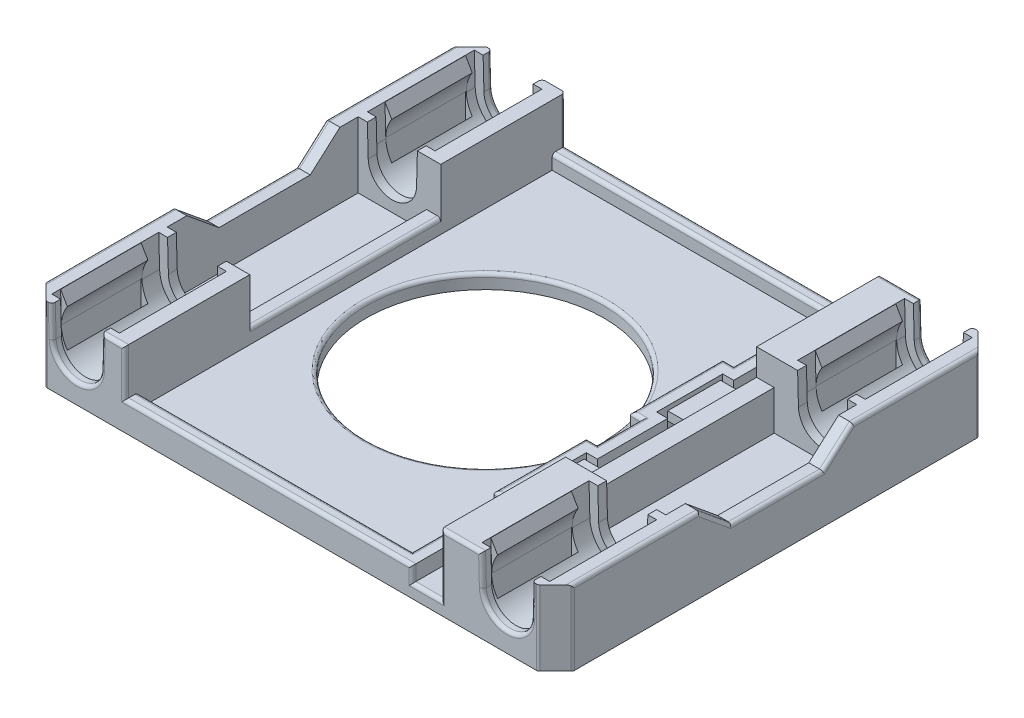
SolidWorks part; units mm, degrees
ref_plane "Front" through (0, 0, 0) normal (0, 0, 1) x (1, 0, 0)
ref_plane "Top" through (0, 0, 0) normal (0, 1, 0) x (1, 0, 0)
ref_plane "Right" through (0, 0, 0) normal (1, 0, 0) x (0, 0, -1)
sketch "Sketch1" plane through (0, 0, 0) normal (0, 1, 0) x (1, 0, 0)
  line L1 (-62.38, 50) -> (62.38, 50)
  line L2 (-62.38, 50) -> (-62.38, -50)
  line L3 (-62.38, -50) -> (62.38, -50)
  line L4 (62.38, 50) -> (62.38, -50)
  dimension "D1" = 124.76
  dimension "D2" = 100
  dimension "6" = 62.38
  dimension "D4" = 50
extrude "Boss-Extrude1" add sketch "Sketch1" along normal blind 20
sketch "Sketch2" plane through (0, 0, 50) normal (0, 0, 1) x (1, 0, 0)
  line L0 (-62.38, 0) -> (62.38, 0) construction
  line L1 (-62.38, 20) -> (-62.38, 0) construction
  line L2 (62.38, 20) -> (62.38, 0) construction
  circle A0 centre (-48.88, 10) radius 7.495
  circle A1 centre (48.88, 10) radius 7.495
  dimension "D2" = 14.99
  dimension "D3" = 14.99
  dimension "D1" = 13.5
  dimension "D4" = 10
  dimension "D5" = 10
  dimension "D6" = 13.5
  dimension "D7" = 97.76
extrude "Cut-Extrude1" cut sketch "Sketch2" against normal through all
sketch "Sketch4" plane through (-62.38, 0, 0) normal (-1, 0, 0) x (0, 0, 1)
  line L0 (-50, 20) -> (50, 20) construction
  line L1 (48, 2) -> (-48, 2)
  line L2 (48, 2) -> (48, 20)
  line L3 (48, 20) -> (-48, 20)
  line L4 (-48, 2) -> (-48, 20)
  line L5 (-50, 0) -> (50, 0) construction
  line L6 (50, 2.505) -> (50, 17.495) construction
  line L9 (-50, 20) -> (-50, 0) construction
  dimension "D1" = 2
  dimension "D2" = 2
  dimension "D3" = 2
extrude "Cut-Extrude2" cut sketch "Sketch4" against normal blind 21.26
sketch "Sketch5" plane through (62.38, 0, 0) normal (1, 0, 0) x (0, 0, -1)
  line L0 (-50, 20) -> (50, 20) construction
  line L1 (-48, 2) -> (48, 2)
  line L2 (-48, 2) -> (-48, 20)
  line L3 (-48, 20) -> (48, 20)
  line L4 (48, 2) -> (48, 20)
  line L5 (-50, 0) -> (50, 0) construction
  line L6 (-50, 20) -> (-50, 0) construction
  line L7 (50, 20) -> (50, 0) construction
  dimension "D1" = 2
  dimension "D2" = 2
  dimension "D3" = 2
extrude "Cut-Extrude3" cut sketch "Sketch5" against normal blind 24.5
sketch "Sketch6" plane through (0, 0, 48) normal (0, 0, -1) x (-1, 0, 0)
  line L0 (41.12, 20) -> (62.38, 20) construction
  line L1 (37.88, 20) -> (59.88, 20)
  line L2 (37.88, 20) -> (37.88, 2)
  line L3 (37.88, 2) -> (59.88, 2)
  line L4 (59.88, 20) -> (59.88, 2)
  line L5 (41.12, 2) -> (62.38, 2) construction
  circle A0 centre (48.88, 10) radius 7.495 construction
  circle A1 centre (48.88, 10) radius 7.495
  dimension "D1" = 22
  dimension "D2" = 11
extrude "Boss-Extrude2" add sketch "Sketch6" along normal blind 24.3
mirror "Mirror1" about plane through (0, 0, 0) normal (0, 0, 1) of "Boss-Extrude2"
mirror "Mirror2" about plane through (0, 0, 0) normal (1, 0, 0) of "Mirror1", "Boss-Extrude2"
sketch "Sketch7" plane through (0, 0, 50) normal (0, 0, 1) x (1, 0, 0)
  line L0 (41.3877, 9.8) -> (41.1154, 20)
  line L2 (-62.38, 20) -> (62.38, 20) construction
  line L3 (41.1154, 20) -> (56.6446, 20)
  line L4 (56.6446, 20) -> (56.3723, 9.8)
  circle A1 centre (48.88, 10) radius 7.495 construction
  arc A2 (41.3877, 9.8) -> (56.3723, 9.8) centre (48.88, 10) ccw
  dimension "D1" = 0.2
  dimension "D2" = 0.2
extrude "Cut-Extrude4" cut sketch "Sketch7" against normal blind 4
mirror "Mirror3" about plane through (0, 0, 0) normal (1, 0, 0) of "Cut-Extrude4"
mirror "Mirror4" about plane through (0, 0, 0) normal (0, 0, 1) of "Mirror3", "Cut-Extrude4"
sketch "Sketch8" plane through (0, 0, -23.7) normal (0, 0, 1) x (1, 0, 0)
  line L0 (56.3723, 9.8) -> (56.6446, 20) construction
  line L1 (41.1154, 20) -> (41.3877, 9.8) construction
  line L2 (56.3723, 9.8) -> (56.6446, 20)
  line L3 (41.1154, 20) -> (41.3877, 9.8)
  line L4 (56.6446, 20) -> (41.1154, 20)
  arc A0 (41.3877, 9.8) -> (56.3723, 9.8) centre (48.88, 10) ccw construction
  arc A1 (41.3877, 9.8) -> (56.3723, 9.8) centre (48.88, 10) ccw
extrude "Cut-Extrude5" cut sketch "Sketch8" against normal blind 4
mirror "Mirror5" about plane through (0, 0, 0) normal (1, 0, 0) of "Cut-Extrude5"
mirror "Mirror6" about plane through (0, 0, 0) normal (0, 0, 1) of "Mirror5", "Cut-Extrude5"
sketch "Sketch10" plane through (0, 0, -46) normal (0, 0, -1) x (-1, 0, 0)
  line L0 (55.0281, 14.2868) -> (56.5631, 16.9454)
  line L1 (56.3723, 9.8) -> (56.6446, 20) construction
  line L2 (56.5631, 16.9454) -> (56.6446, 20)
  line L3 (56.6446, 20) -> (41.1154, 20)
  line L4 (41.1154, 20) -> (41.1969, 16.9454)
  line L5 (41.1154, 20) -> (41.3877, 9.8) construction
  line L6 (41.1969, 16.9454) -> (42.7319, 14.2868)
  arc A0 (56.3723, 9.8) -> (41.3877, 9.8) centre (48.88, 10) ccw construction
  arc A1 (55.0281, 14.2868) -> (42.7319, 14.2868) centre (48.88, 10) ccw
  dimension "D2" = 60
  dimension "D1" = 60
  dimension "D3" = 3.07
extrude "Cut-Extrude6" cut sketch "Sketch10" against normal through all both and the other way through all
mirror "Mirror7" about plane through (0, 0, 0) normal (1, 0, 0) of "Cut-Extrude6"
ref_plane "Plane6" through (0, 10, 0) normal (0, 1, 0) x (1, 0, 0)
sketch "Sketch11" plane through (0, 10, 0) normal (0, 1, 0) x (1, 0, 0)
  line L4 (42.7319, -46) -> (42.7319, -27.7)
  line L5 (42.7319, -46) -> (42.7319, -27.7)
  line L6 (41.1969, -27.7) -> (41.1969, -46)
  line L7 (42.7319, -27.7) -> (41.1969, -27.7)
  line L8 (42.7319, -27.7) -> (41.1969, -27.7)
  line L9 (41.1969, -46) -> (42.7319, -46)
  line L10 (41.1969, -27.7) -> (41.1969, -46)
  line L11 (41.1969, -46) -> (42.7319, -46)
  line L12 (56.5631, -46) -> (56.5631, -27.7)
  line L13 (56.5631, -27.7) -> (55.0281, -27.7)
  line L14 (55.0281, -27.7) -> (55.0281, -46)
  line L15 (55.0281, -46) -> (56.5631, -46)
  line L16 (56.5631, -46) -> (56.5631, -27.7)
  line L17 (56.5631, -27.7) -> (55.0281, -27.7)
  line L18 (55.0281, -27.7) -> (55.0281, -46)
  line L19 (55.0281, -46) -> (56.5631, -46)
  dimension "D1" = 0
  dimension "D2" = 0
extrude "Cut-Extrude7" cut sketch "Sketch11" against normal through all
mirror "Mirror8" about plane through (0, 0, 0) normal (1, 0, 0) of "Cut-Extrude7"
mirror "Mirror9" about plane through (0, 0, 0) normal (0, 0, 1) of "Mirror8", "Cut-Extrude7"
sketch "Sketch12" plane through (0, 0, -50) normal (0, 0, -1) x (-1, 0, 0)
  line L2 (54.6453, 20.0534) -> (62.38, 20)
  line L3 (62.38, 20) -> (62.38, 0)
  line L4 (43.1147, 20.0534) -> (43.387, 9.8534)
  line L5 (54.373, 9.8534) -> (54.6453, 20.0534)
  line L6 (43.1147, 20.0534) -> (43.387, 9.8534)
  line L7 (54.373, 9.8534) -> (54.6453, 20.0534)
  line L8 (62.38, 0) -> (30.8026, 0)
  line L9 (-62.38, 0) -> (62.38, 0) construction
  line L10 (30.8026, 0) -> (30.8026, 20)
  line L11 (-41.1154, 20) -> (41.1154, 20) construction
  line L12 (30.8026, 20) -> (43.1147, 20.0534)
  arc A2 (43.387, 9.8534) -> (54.373, 9.8534) centre (48.88, 10) ccw
  arc A3 (43.387, 9.8534) -> (54.373, 9.8534) centre (48.88, 10) ccw
  dimension "D1" = 2
extrude "Boss-Extrude3" add sketch "Sketch12" against normal blind 2
mirror "Mirror10" about plane through (0, 0, 0) normal (1, 0, 0) of "Boss-Extrude3"
mirror "Mirror11" about plane through (0, 0, 0) normal (0, 0, 1) of "Boss-Extrude3", "Mirror10"
sketch "Sketch13" plane through (0, 0, 23.7) normal (0, 0, -1) x (-1, 0, 0)
  line L0 (54.6453, 20.0534) -> (54.373, 9.8534) construction
  line L1 (43.387, 9.8534) -> (43.1147, 20.0534) construction
  line L2 (54.6453, 20.0534) -> (54.373, 9.8534)
  line L3 (43.387, 9.8534) -> (43.1147, 20.0534)
  line L4 (56.6446, 20) -> (54.6453, 20.0534)
  line L5 (56.6446, 20) -> (59.88, 20)
  line L6 (59.88, 20) -> (59.88, 2)
  line L7 (41.12, 2) -> (59.88, 2) construction
  line L8 (59.88, 2) -> (35.5, 2)
  line L9 (35.5, 2) -> (35.5, 20)
  line L11 (35.5, 20) -> (43.1147, 20.0534)
  arc A0 (43.387, 9.8534) -> (54.373, 9.8534) centre (48.88, 10) ccw construction
  arc A1 (43.387, 9.8534) -> (54.373, 9.8534) centre (48.88, 10) ccw
extrude "Boss-Extrude4" add sketch "Sketch13" along normal blind 2
mirror "Mirror12" about plane through (0, 0, 0) normal (1, 0, 0) of "Boss-Extrude4"
mirror "Mirror13" about plane through (0, 0, 0) normal (0, 0, 1) of "Mirror12", "Boss-Extrude4"
sketch "Sketch14" plane through (0, 0, 0) normal (0, -1, 0) x (1, 0, 0)
  line L0 (59.88, 21.7) -> (59.88, 48) construction
  line L1 (59.88, -50) -> (59.88, 50)
  line L2 (-62.38, 50) -> (62.38, 50) construction
  line L3 (62.38, 50) -> (62.38, -50) construction
  line L4 (62.38, 50) -> (62.38, -50)
  line L5 (59.88, 50) -> (62.38, 50)
  line L6 (59.88, -50) -> (62.38, -50)
extrude "Cut-Extrude9" cut sketch "Sketch14" against normal through all
mirror "Mirror15" about plane through (0, 0, 0) normal (1, 0, 0) of "Cut-Extrude9"
sketch "Sketch15" plane through (0, 20, 0) normal (0, 1, 0) x (1, 0, 0)
  line L0 (33.88, -50) -> (33.88, 50)
  line L1 (-30.8026, -50) -> (30.8026, -50) construction
  line L2 (30.8026, 50) -> (-30.8026, 50) construction
  line L3 (59.88, -21.7) -> (59.88, 21.7) construction
  line L4 (27.38, -50) -> (27.38, 50)
  line L5 (27.38, 50) -> (33.88, 50)
  line L6 (33.88, -50) -> (27.38, -50)
  dimension "D1" = 26
  dimension "D2" = 6.5
extrude "Cut-Extrude10" cut sketch "Sketch15" against normal blind 17
sketch "Sketch16" plane through (0, 2, 0) normal (0, 1, 0) x (1, 0, 0)
  line L2 (-59.88, 21.7) -> (-59.88, -21.7)
  line L3 (-59.88, -21.7) -> (-56.6446, -21.7)
  line L4 (-41.12, -21.7) -> (-59.88, -21.7) construction
  line L5 (-59.88, 21.7) -> (-56.6446, 21.7)
  line L6 (-56.6446, 23.7) -> (-56.6446, 48) construction
  line L7 (-56.6446, -21.7) -> (-56.6446, 21.7)
extrude "Boss-Extrude6" add sketch "Sketch16" along normal up to vertex up to point (-59.88, 20, -48)
mirror "Mirror16" about plane through (0, 0, 0) normal (1, 0, 0) of "Boss-Extrude6"
sketch "Sketch17" plane through (59.88, 0, 0) normal (1, 0, 0) x (0, 0, -1)
  line L0 (20.9433, 20) -> (10.8, 11)
  line L1 (10.8, 11) -> (-9.9399, 11)
  line L2 (-9.9399, 11) -> (-20.9009, 20)
  line L3 (48, 20) -> (-48, 20) construction
  line L4 (50, 10) -> (-50, 10) construction
  line L5 (20.9433, 20) -> (-20.9009, 20)
  dimension "D1" = 1
extrude "Cut-Extrude11" cut sketch "Sketch17" against normal blind 16
mirror "Mirror17" about plane through (0, 0, 0) normal (1, 0, 0) of "Cut-Extrude11"
sketch "Sketch18" plane through (0, 0, 0) normal (0, -1, 0) x (1, 0, 0)
  line L1 (24.88, 8) -> (24.88, 23)
  line L2 (33.88, 50) -> (33.88, -50) construction
  line L3 (33.88, 23) -> (33.88, 8)
  line L5 (33.88, 23) -> (24.88, 23)
  line L6 (50, 0) -> (-50, 0) construction
  line L7 (24.88, 8) -> (33.88, 8)
  dimension "D1" = 23
  dimension "D2" = 15
  dimension "D3" = 9
extrude "Cut-Extrude12" cut sketch "Sketch18" against normal blind 25
mirror "Mirror18" about plane through (0, 0, 0) normal (0, 0, 1) of "Cut-Extrude12"
sketch "Sketch19" plane through (33.88, 0, 0) normal (-1, 0, 0) x (0, 0, 1)
  line L0 (-8, 0) -> (-23, 0) construction
  line L1 (-21.5, 6.5) -> (-9.5, 6.5)
  line L2 (-21.5, 6.5) -> (-21.5, 4.5)
  line L3 (-21.5, 4.5) -> (-9.5, 4.5)
  line L4 (-9.5, 6.5) -> (-9.5, 4.5)
  line L5 (-8, 3) -> (-8, 0) construction
  line L6 (-23, 3) -> (-23, 0) construction
  dimension "D1" = 4.5
  dimension "D2" = 2
  dimension "D3" = 1.5
  dimension "D4" = 1.5
extrude "Boss-Extrude7" add sketch "Sketch19" along normal blind 8
mirror "Mirror19" about plane through (0, 0, 0) normal (0, 0, 1) of "Boss-Extrude7"
sketch "Sketch21" plane through (0, 20, 0) normal (0, 1, 0) x (1, 0, 0)
  line L2 (-41.12, 21.7) -> (-41.12, -21.7) construction
  line L6 (27.38, 50) -> (-30.8026, 50) construction
  circle A0 centre (-6.12, 0) radius 27
  dimension "D1" = 54
  dimension "D2" = 35
  dimension "D3" = 50
extrude "Cut-Extrude13" cut sketch "Sketch21" against normal through all
sketch "Sketch23" plane through (0, 0, 50) normal (0, 0, 1) x (1, 0, 0)
  line L0 (-59.88, 20.5) -> (59.88, 20.5)
  line L2 (-59.88, 0) -> (59.88, 0) construction
  line L3 (59.88, 17) -> (-59.88, 17)
  line L4 (59.88, 20.0172) -> (59.88, 0) construction
  line L6 (-59.88, 20.0172) -> (-59.88, 0) construction
  line L7 (-59.88, 17) -> (-59.88, 20.5)
  line L8 (59.88, 17) -> (59.88, 20.5)
  dimension "D1" = 17
extrude "Cut-Extrude18" cut sketch "Sketch23" against normal through all
sketch "Sketch26" plane through (0, 17, 0) normal (0, 1, 0) x (1, 0, 0)
  line L0 (-43.1962, 50) -> (27.38, 50) construction
  line L1 (27.38, -50) -> (-37.885, -50)
  line L2 (27.38, -50) -> (27.38, 50)
  line L3 (27.38, 50) -> (-37.885, 50)
  line L4 (-37.885, -50) -> (-37.885, 50)
extrude "Cut-Extrude19" cut sketch "Sketch26" against normal blind 6.02
sketch "Sketch27" plane through (-37.885, 0, 0) normal (1, 0, 0) x (0, 0, -1)
  line L0 (-21.7, 17) -> (-21.7, 2) construction
  line L1 (21.7, 2) -> (21.7, 17) construction
  line L2 (-21.7, 17) -> (-21.7, 10.98)
  line L3 (21.7, 10.98) -> (21.7, 17)
  line L4 (-21.7, 17) -> (21.7, 17)
  line L6 (50, 10.98) -> (-50, 10.98) construction
  line L8 (21.7, 10.98) -> (-21.7, 10.98)
extrude "Cut-Extrude20" cut sketch "Sketch27" against normal blind 6
sketch "Sketch28" plane through (37.88, 0, 0) normal (1, 0, 0) x (0, 0, -1)
  line L0 (21.7, 2) -> (21.7, 17) construction
  line L1 (-21.7, 17) -> (21.7, 17)
  line L2 (-21.7, 17) -> (-21.7, 10.98)
  line L3 (-21.7, 10.98) -> (21.7, 10.98)
  line L4 (21.7, 17) -> (21.7, 10.98)
  dimension "D1" = 6.02
extrude "Cut-Extrude21" cut sketch "Sketch28" against normal blind 6
sketch "Sketch31" plane through (0, 10.98, 0) normal (0, 1, 0) x (1, 0, 0)
  line L0 (27.38, 23) -> (27.38, 50) construction
  line L1 (27.38, 50) -> (-37.885, 50) construction
  line L2 (-37.885, 50) -> (-37.885, 21.7) construction
  line L3 (-41.12, 21.7) -> (-37.885, 21.7) construction
  line L4 (-41.12, 21.7) -> (-41.12, -21.7) construction
  line L5 (-41.12, -21.7) -> (-37.885, -21.7) construction
  line L6 (-37.885, -21.7) -> (-37.885, -50) construction
  line L7 (-37.885, -50) -> (27.38, -50) construction
  line L8 (27.38, -50) -> (27.38, -23) construction
  line L9 (27.38, -23) -> (24.88, -23) construction
  line L10 (24.88, -23) -> (24.88, -8) construction
  line L11 (27.38, -8) -> (27.38, 8) construction
  line L12 (24.88, -8) -> (27.38, -8) construction
  line L13 (24.88, 23) -> (24.88, 8) construction
  line L14 (24.88, 8) -> (27.38, 8) construction
  line L15 (27.38, 23) -> (24.88, 23) construction
  line L16 (27.38, 23) -> (27.38, 50)
  line L17 (27.38, 50) -> (-37.885, 50)
  line L18 (-37.885, 50) -> (-37.885, 21.7)
  line L19 (-41.12, 21.7) -> (-37.885, 21.7)
  line L20 (-41.12, 21.7) -> (-41.12, -21.7)
  line L21 (-41.12, -21.7) -> (-37.885, -21.7)
  line L22 (-37.885, -21.7) -> (-37.885, -50)
  line L23 (-37.885, -50) -> (27.38, -50)
  line L24 (27.38, -50) -> (27.38, -23)
  line L25 (27.38, -23) -> (24.88, -23)
  line L26 (24.88, -23) -> (24.88, -8)
  line L27 (27.38, -8) -> (27.38, 8)
  line L28 (24.88, -8) -> (27.38, -8)
  line L29 (24.88, 23) -> (24.88, 8)
  line L30 (24.88, 8) -> (27.38, 8)
  line L31 (27.38, 23) -> (24.88, 23)
extrude "Cut-Extrude25" cut sketch "Sketch31" against normal blind 4.48
sketch "Sketch29" plane through (0, 6.5, 0) normal (0, 1, 0) x (1, 0, 0)
  line L8 (-37.885, 47) -> (-37.885, -47)
  line L19 (24.38, 47) -> (24.38, 26)
  line L20 (24.38, 26) -> (21.88, 26)
  line L21 (21.88, 26) -> (21.88, 5)
  line L22 (21.88, 5) -> (24.38, 5)
  line L23 (24.38, 5) -> (24.38, -5)
  line L24 (24.38, -5) -> (21.88, -5)
  line L25 (21.88, -5) -> (21.88, -26)
  line L26 (21.88, -26) -> (24.38, -26)
  line L27 (24.38, -26) -> (24.38, -47)
  line L33 (-37.885, -47) -> (24.38, -47)
  line L35 (24.38, 47) -> (-37.885, 47)
  circle A1 centre (-6.12, 0) radius 27
  point P37 (27.38, 5)
  point P38 (24.38, 8)
extrude "Cut-Extrude23" cut sketch "Sketch29" against normal blind 3.3
sketch "Sketch30" plane through (0, 0, 0) normal (0, -1, 0) x (1, 0, 0)
  line L0 (-55.88, 50) -> (-59.88, 46)
  line L1 (-59.88, 50) -> (59.88, 50) construction
  line L2 (-59.88, 50) -> (-59.88, -50) construction
  line L3 (-59.88, 50) -> (-55.88, 50)
  line L4 (-59.88, 50) -> (-59.88, 46)
  dimension "D1" = 4
extrude "Cut-Extrude24" cut sketch "Sketch30" against normal through all
mirror "Mirror20" about plane through (0, 0, 0) normal (0, 0, 1) of "Cut-Extrude24"
mirror "Mirror21" about plane through (0, 0, 0) normal (1, 0, 0) of "Mirror20", "Cut-Extrude24"
fillet "Fillet3" radius 0.8 56 edges at (-6.12, 3.2, 27) (-55.88, 8.5, 50) (-54.4684, 13.4267, 50) (-48.88, 4.505, 50) (-43.2916, 13.4267, 50) (-40.5406, 17, 50) (-37.885, 11.75, 50) (27.38, 4.75, 50) (30.63, 3, 50) (33.88, 10, 50) (38.5381, 17, 50) (43.2916, 13.4267, 50) (48.88, 4.505, 50) (54.4684, 13.4267, 50) (55.88, 8.5, 50) (59.88, 8.5, 46) (59.88, 17, 31.6236) (59.88, 14, 13.5936) (59.88, 11, -0.4301) (59.88, 14, -14.1811) (59.88, 17, -31.7811) (59.88, 8.5, -46) (54.4684, 13.4267, -50) (48.88, 4.505, -50) (43.2916, 13.4267, -50) (38.5381, 17, -50) (33.88, 10, -50) (30.63, 3, -50) (27.38, 4.75, -50) (-37.885, 11.75, -50) (-43.2916, 13.4267, -50) (-48.88, 4.505, -50) (-54.4684, 13.4267, -50) (-55.88, 8.5, -50) (55.88, 8.5, -50) (-59.88, 8.5, 46) (-59.88, 8.5, -46) (-37.885, 6.5, 0) (-6.7525, 6.5, -47) (-6.7525, 6.5, 47) (24.38, 6.5, 36.5) (23.13, 6.5, 26) (21.88, 6.5, 15.5) (23.13, 6.5, 5) (24.38, 6.5, 0) (23.13, 6.5, -5) (21.88, 6.5, -15.5) (23.13, 6.5, -26) (24.38, 6.5, -36.5) (-59.88, 17, 31.6236) (-59.88, 14, 13.5936) (-59.88, 11, -0.4301) (-59.88, 14, -14.1811) (-59.88, 17, -31.7811) (-5.2525, 6.5, 50) (-5.2525, 6.5, -50)
